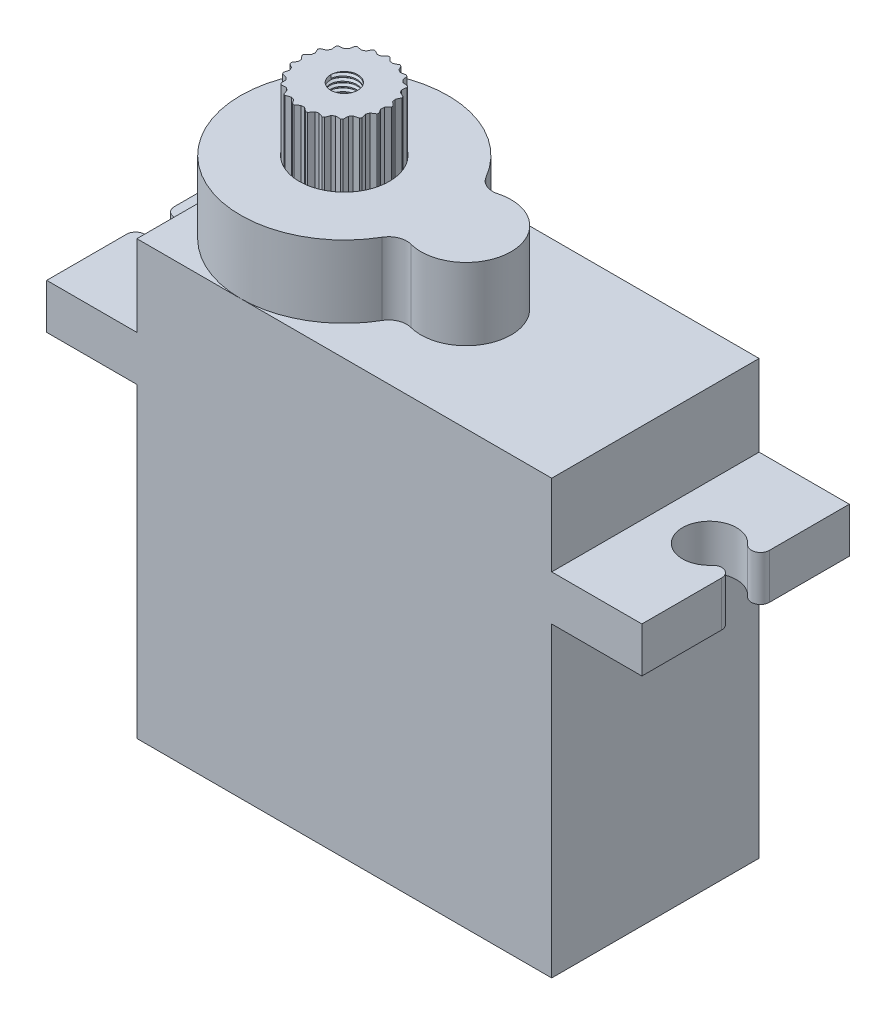
SolidWorks part; units mm, degrees
ref_plane "Front Plane" through (0, 0, 0) normal (0, 0, 1) x (1, 0, 0)
ref_plane "Top Plane" through (0, 0, 0) normal (0, 1, 0) x (1, 0, 0)
ref_plane "Right Plane" through (0, 0, 0) normal (1, 0, 0) x (0, 0, -1)
sketch "Sketch1" plane through (0, 0, 0) normal (0, 0, 1) x (1, 0, 0)
  line L0 (23, 17) -> (28, 17)
  line L1 (0, 0) -> (23, 0)
  line L2 (0, 0) -> (0, 17)
  line L3 (0, 24) -> (23, 24)
  line L4 (23, 0) -> (23, 17)
  line L5 (28, 17) -> (28, 19.5)
  line L6 (28, 19.5) -> (23, 19.5)
  line L7 (11.5, 24) -> (11.5, 0) construction
  line L8 (-5, 19.5) -> (0, 19.5)
  line L9 (-5, 17) -> (-5, 19.5)
  line L10 (0, 17) -> (-5, 17)
  line L11 (0, 19.5) -> (0, 24)
  line L12 (23, 19.5) -> (23, 24)
  dimension "D1" = 23
  dimension "D2" = 24
  dimension "D3" = 17
  dimension "D4" = 2.5
  dimension "D5" = 5
extrude "Boss-Extrude1" add sketch "Sketch1" along normal blind 11.5
sketch "Sketch2" plane through (0, 19.5, 0) normal (0, 1, 0) x (1, 0, 0)
  line L0 (-5, -5.75) -> (0, -5.75) construction
  line L1 (-5, -11.5) -> (-5, 0) construction
  line L2 (0, -11.5) -> (0, 0) construction
  line L3 (-5, -4.4271) -> (-5, -7.0729)
  arc A0 (-4.125, -6.7422) -> (-4.125, -4.7578) centre (-3, -5.75) ccw
  arc A1 (-5, -4.4271) -> (-4.125, -4.7578) centre (-4.5, -4.4271) ccw
  arc A2 (-5, -7.0729) -> (-4.125, -6.7422) centre (-4.5, -7.0729) cw
  dimension "D1" = 3
  dimension "D3" = 1
  dimension "D2" = 3
extrude "Cut-Extrude1" cut sketch "Sketch2" against normal blind 12
sketch "Sketch3" plane through (0, 19.5, 0) normal (0, 1, 0) x (1, 0, 0)
  line L0 (28, -5.75) -> (23, -5.75) construction
  line L1 (28, -11.5) -> (28, 0) construction
  line L2 (23, -11.5) -> (23, 0) construction
  line L3 (23, -11.5) -> (23, 0) construction
  line L4 (28, -4.4271) -> (28, -7.0729)
  arc A0 (27.125, -4.7578) -> (27.125, -6.7422) centre (26, -5.75) ccw
  arc A1 (27.125, -4.7578) -> (28, -4.4271) centre (27.5, -4.4271) ccw
  arc A2 (28, -7.0729) -> (27.125, -6.7422) centre (27.5, -7.0729) ccw
  dimension "D1" = 1
  dimension "D2" = 1
  dimension "D3" = 3
  dimension "D4" = 3
extrude "Cut-Extrude2" cut sketch "Sketch3" against normal blind 12
sketch "Sketch4" plane through (0, 24, 0) normal (0, 1, 0) x (1, 0, 0)
  line L0 (0, -11.5) -> (0, 0) construction
  line L1 (23, 0) -> (0, 0) construction
  line L2 (23, -11.5) -> (23, 0) construction
  line L3 (0, -5.75) -> (23, -5.75) construction
  line L4 (23, -11.5) -> (0, -11.5) construction
  arc A0 (10.727, -2.8705) -> (10.727, -8.6295) centre (5.75, -5.75) ccw
  arc A1 (11.8519, -8.1645) -> (11.8519, -3.3355) centre (12.5, -5.75) ccw
  arc A2 (10.727, -2.8705) -> (11.8519, -3.3355) centre (11.5926, -2.3697) ccw
  arc A3 (10.727, -8.6295) -> (11.8519, -8.1645) centre (11.5926, -9.1303) cw
  dimension "D1" = 11.5
  dimension "D2" = 5
  dimension "D3" = 10.5
  dimension "D4" = 5.75
  dimension "D5" = 2
extrude "Boss-Extrude2" add sketch "Sketch4" along normal blind 4
sketch "Sketch5" plane through (0, 28, 0) normal (0, 1, 0) x (1, 0, 0)
  circle A0 centre (5.75, -5.75) radius 2.5
  dimension "D1" = 5
extrude "Cut-Extrude3" cut sketch "Sketch5" against normal blind 6
sketch "Sketch6" plane through (0, 22, 0) normal (0, 1, 0) x (1, 0, 0)
  line L0 (5.75, -3.45) -> (5.75, -3.2625) construction
  line L1 (5.75, -3.2625) -> (5.8, -3.2625)
  line L2 (5.75, -3.2625) -> (5.7, -3.2625)
  line L3 (5.7, -3.2625) -> (5.5, -3.4636)
  line L4 (5.8, -3.2625) -> (6, -3.4636)
  line L7 (6.531, -3.3877) -> (6.6628, -3.6389)
  line L8 (6.4832, -3.373) -> (6.531, -3.3877)
  line L9 (6.4832, -3.373) -> (6.4354, -3.3583)
  line L10 (6.4354, -3.3583) -> (6.185, -3.4915)
  line L12 (7.1926, -3.7229) -> (7.2445, -4.0017)
  line L13 (7.1513, -3.6947) -> (7.1926, -3.7229)
  line L14 (7.1513, -3.6947) -> (7.11, -3.6666)
  line L15 (7.11, -3.6666) -> (6.8314, -3.7201)
  line L17 (7.726, -4.2382) -> (7.6934, -4.5199)
  line L18 (7.6948, -4.1991) -> (7.726, -4.2382)
  line L19 (7.6948, -4.1991) -> (7.6636, -4.16)
  line L20 (7.6636, -4.16) -> (7.3817, -4.129)
  line L22 (8.0838, -4.8878) -> (7.9697, -5.1474)
  line L23 (8.0656, -4.8412) -> (8.0838, -4.8878)
  line L24 (8.0656, -4.8412) -> (8.0473, -4.7947)
  line L25 (8.0473, -4.7947) -> (7.787, -4.682)
  line L27 (8.2343, -5.614) -> (8.0487, -5.8284)
  line L28 (8.2306, -5.5641) -> (8.2343, -5.614)
  line L29 (8.2306, -5.5641) -> (8.2268, -5.5142)
  line L30 (8.2268, -5.5142) -> (8.0113, -5.3298)
  line L32 (8.164, -6.3523) -> (7.9234, -6.5025)
  line L33 (8.1751, -6.3035) -> (8.164, -6.3523)
  line L34 (8.1751, -6.3035) -> (8.1863, -6.2548)
  line L35 (8.1863, -6.2548) -> (8.0347, -6.015)
  line L37 (7.8792, -7.0371) -> (7.6051, -7.1097)
  line L38 (7.9042, -6.9938) -> (7.8792, -7.0371)
  line L39 (7.9042, -6.9938) -> (7.9292, -6.9505)
  line L40 (7.9292, -6.9505) -> (7.8551, -6.6767)
  line L42 (7.4053, -7.6075) -> (7.1219, -7.5961)
  line L43 (7.4419, -7.5735) -> (7.4053, -7.6075)
  line L44 (7.4419, -7.5735) -> (7.4786, -7.5395)
  line L45 (7.4786, -7.5395) -> (7.4884, -7.256)
  line L47 (6.7842, -8.0129) -> (6.5168, -7.9184)
  line L48 (6.8293, -7.9912) -> (6.7842, -8.0129)
  line L49 (6.8293, -7.9912) -> (6.8743, -7.9695)
  line L50 (6.8743, -7.9695) -> (6.9673, -7.7015)
  line L52 (6.0713, -8.2172) -> (5.8436, -8.0481)
  line L53 (6.1207, -8.2097) -> (6.0713, -8.2172)
  line L54 (6.1207, -8.2097) -> (6.1702, -8.2023)
  line L55 (6.1702, -8.2023) -> (6.338, -7.9736)
  line L57 (5.3298, -8.2023) -> (5.162, -7.9736)
  line L58 (5.3793, -8.2097) -> (5.3298, -8.2023)
  line L59 (5.3793, -8.2097) -> (5.4287, -8.2172)
  line L60 (5.4287, -8.2172) -> (5.6564, -8.0481)
  line L62 (4.6257, -7.9695) -> (4.5327, -7.7015)
  line L63 (4.6707, -7.9912) -> (4.6257, -7.9695)
  line L64 (4.6707, -7.9912) -> (4.7158, -8.0129)
  line L65 (4.7158, -8.0129) -> (4.9832, -7.9184)
  line L67 (4.0214, -7.5395) -> (4.0116, -7.256)
  line L68 (4.0581, -7.5735) -> (4.0214, -7.5395)
  line L69 (4.0581, -7.5735) -> (4.0947, -7.6075)
  line L70 (4.0947, -7.6075) -> (4.3781, -7.5961)
  line L72 (3.5708, -6.9505) -> (3.6449, -6.6767)
  line L73 (3.5958, -6.9938) -> (3.5708, -6.9505)
  line L74 (3.5958, -6.9938) -> (3.6208, -7.0371)
  line L75 (3.6208, -7.0371) -> (3.8949, -7.1097)
  line L77 (3.3137, -6.2548) -> (3.4653, -6.015)
  line L78 (3.3249, -6.3035) -> (3.3137, -6.2548)
  line L79 (3.3249, -6.3035) -> (3.336, -6.3523)
  line L80 (3.336, -6.3523) -> (3.5766, -6.5025)
  line L82 (3.2732, -5.5142) -> (3.4887, -5.3298)
  line L83 (3.2694, -5.5641) -> (3.2732, -5.5142)
  line L84 (3.2694, -5.5641) -> (3.2657, -5.614)
  line L85 (3.2657, -5.614) -> (3.4513, -5.8284)
  line L87 (3.4527, -4.7947) -> (3.713, -4.682)
  line L88 (3.4344, -4.8412) -> (3.4527, -4.7947)
  line L89 (3.4344, -4.8412) -> (3.4162, -4.8878)
  line L90 (3.4162, -4.8878) -> (3.5303, -5.1474)
  line L92 (3.8364, -4.16) -> (4.1183, -4.129)
  line L93 (3.8052, -4.1991) -> (3.8364, -4.16)
  line L94 (3.8052, -4.1991) -> (3.774, -4.2382)
  line L95 (3.774, -4.2382) -> (3.8066, -4.5199)
  line L97 (4.39, -3.6666) -> (4.6686, -3.7201)
  line L98 (4.3487, -3.6947) -> (4.39, -3.6666)
  line L99 (4.3487, -3.6947) -> (4.3074, -3.7229)
  line L100 (4.3074, -3.7229) -> (4.2555, -4.0017)
  line L102 (5.0646, -3.3583) -> (5.315, -3.4915)
  line L103 (5.0168, -3.373) -> (5.0646, -3.3583)
  line L104 (5.0168, -3.373) -> (4.969, -3.3877)
  line L105 (4.969, -3.3877) -> (4.8372, -3.6389)
  arc A2 (4.8372, -3.6389) -> (4.6686, -3.7201) centre (5.75, -5.75) ccw
  arc A4 (6.185, -3.4915) -> (6, -3.4636) centre (5.75, -5.75) ccw
  arc A5 (6.8314, -3.7201) -> (6.6628, -3.6389) centre (5.75, -5.75) ccw
  arc A6 (7.3817, -4.129) -> (7.2445, -4.0017) centre (5.75, -5.75) ccw
  arc A7 (7.787, -4.682) -> (7.6934, -4.5199) centre (5.75, -5.75) ccw
  arc A8 (8.0113, -5.3298) -> (7.9697, -5.1474) centre (5.75, -5.75) ccw
  arc A9 (8.0347, -6.015) -> (8.0487, -5.8284) centre (5.75, -5.75) ccw
  arc A10 (7.8551, -6.6767) -> (7.9234, -6.5025) centre (5.75, -5.75) ccw
  arc A11 (7.4884, -7.256) -> (7.6051, -7.1097) centre (5.75, -5.75) ccw
  arc A12 (6.9673, -7.7015) -> (7.1219, -7.5961) centre (5.75, -5.75) ccw
  arc A13 (6.338, -7.9736) -> (6.5168, -7.9184) centre (5.75, -5.75) ccw
  arc A14 (5.6564, -8.0481) -> (5.8436, -8.0481) centre (5.75, -5.75) ccw
  arc A15 (4.9832, -7.9184) -> (5.162, -7.9736) centre (5.75, -5.75) ccw
  arc A16 (3.8949, -7.1097) -> (4.0116, -7.256) centre (5.75, -5.75) ccw
  arc A17 (4.3781, -7.5961) -> (4.5327, -7.7015) centre (5.75, -5.75) ccw
  arc A18 (3.5766, -6.5025) -> (3.6449, -6.6767) centre (5.75, -5.75) ccw
  arc A19 (3.4513, -5.8284) -> (3.4653, -6.015) centre (5.75, -5.75) ccw
  arc A20 (3.5303, -5.1474) -> (3.4887, -5.3298) centre (5.75, -5.75) ccw
  arc A21 (3.8066, -4.5199) -> (3.713, -4.682) centre (5.75, -5.75) ccw
  arc A22 (4.2555, -4.0017) -> (4.1183, -4.129) centre (5.75, -5.75) ccw
  arc A23 (5.5, -3.4636) -> (5.315, -3.4915) centre (5.75, -5.75) ccw
  point P5 (5.75, -3.2598)
  point P6 (0, 0)
  point P7 (5.75, -3.25)
  point P12 (0, 0)
  point P13 (0, 0)
  point P114 (0, 0)
  point P115 (5.75, -3.2625)
  dimension "D1" = 4.6
  dimension "D2" = 0.05
  dimension "D3" = 0.05
  dimension "D4" = 0.5
  dimension "D5" = 21
  dimension "D6" = 0.1875
  dimension "D7" = 0.2011
extrude "Boss-Extrude4" add sketch "Sketch6" along normal blind 9.5
sketch "Sketch11" plane through (0, 31.5, 0) normal (0, 1, 0) x (1, 0, 0)
  circle A0 centre (5.75, -5.75) radius 0.75
  dimension "D1" = 1.5
extrude "Cut-Extrude6" cut sketch "Sketch11" against normal blind 6
thread "Thread2" pitch 0.25 method cut profile "Thread Profile2" start angle 0, offset 0, length 6, pitch 0.25, diameter 1.5
ref_plane "Plane3" through (5, 31.5, 5.75) normal (0, 0, 1) x (-1, 0, 0)
sketch "Thread Profile2" plane through (5, 31.5, 5.75) normal (0, 0, 1) x (-1, 0, 0)
  line L0 (0, 0) -> (0, 0.25) construction
  line L1 (0, 0) -> (0.1353, 0.0781)
  line L2 (0.1353, 0.0781) -> (0.1353, 0.1094)
  line L3 (0.1353, 0.1094) -> (0, 0.1875)
  line L4 (0.1353, 0.0937) -> (0, 0.0937) construction
  line L11 (0, 0) -> (0, 0.1875)
  point P2 (0, 0)
  dimension "Pitch" = 0.25
  dimension "Profile_Angle" = 60
  dimension "Profile_Land" = 0.0312
  dimension "Profile_Height" = 0.1353
